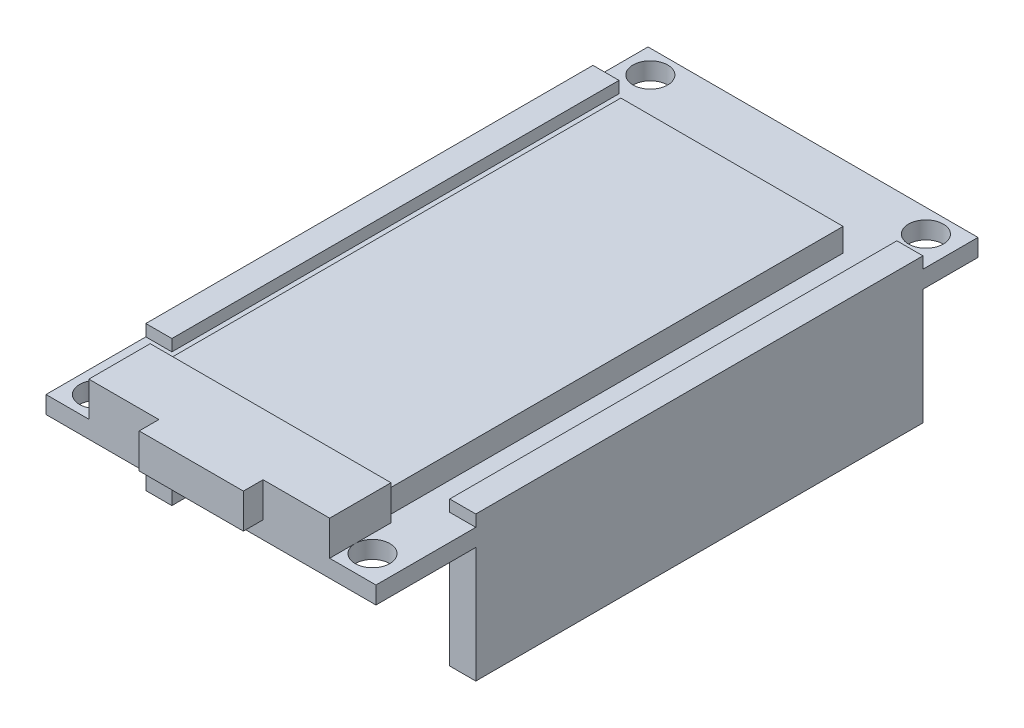
SolidWorks part; units mm, degrees
other "Исправление1"
sketch "Эскиз7"
ref_plane "Спереди" through (0, 0, 0) normal (0, 0, 1) x (1, 0, 0)
ref_plane "Сверху" through (0, 0, 0) normal (0, 1, 0) x (1, 0, 0)
ref_plane "Справа" through (0, 0, 0) normal (1, 0, 0) x (0, 0, -1)
other "Configuration Table"
sketch "Эскиз2" plane through (0, 0, 0) normal (0, 1, 0) x (1, 0, 0)
  line L0 (0.2951, -47.7) -> (-4.7049, -47.7) construction
  line L1 (0, 0) -> (28.5, 0)
  line L2 (0, 0) -> (0, -52)
  line L3 (0, -52) -> (28.5, -52)
  line L4 (28.5, 0) -> (28.5, -52)
  line L5 (29.7573, -47.7) -> (24.7573, -47.7) construction
  line L6 (28.9793, -47.7) -> (23.9793, -47.7) construction
  circle A1 centre (2.2, -2) radius 1.5
  circle A2 centre (26, -2) radius 1.5
  circle A4 centre (2.2, -49.8) radius 1.5
  circle A5 centre (26, -49.8) radius 1.5
  point P4 (2.2, -49.8)
  point P10 (0, 0)
  point P13 (0, 0)
  point P16 (0, 0)
  point P17 (2.2, -49.8)
  dimension "D3" = 2
  dimension "D4" = 2.2
  dimension "D5" = 2.5
  dimension "D6" = 2
  dimension "D7" = 3
  dimension "D8" = 3
  dimension "D9" = 3
  dimension "D10" = 2.2
  dimension "D11" = 2.5
  dimension "D12" = 3
  dimension "D1" = 28.5
  dimension "D2" = 52
extrude "Бобышка-Вытянуть1" add sketch "Эскиз2" along normal blind 1.5
sketch3d "Трехмерный эскиз1"
  line L0 (0, 1.5, 0) -> (0, 1.5, 52) construction
  line L2 (9.75, 1.5, 46.7) -> (9.75, 1.5, 53.7)
  line L3 (9.75, 1.5, 46.7) -> (18.75, 1.5, 46.7)
  line L4 (18.75, 1.5, 46.7) -> (18.75, 1.5, 53.7)
  line L5 (9.75, 1.5, 53.7) -> (18.75, 1.5, 53.7)
  line L6 (0, 1.5, 52) -> (28.5, 1.5, 52) construction
  dimension "D1" = 9
  dimension "D2" = 1.7
  dimension "D3" = 9.75
  dimension "D4" = 7
extrude "Бобышка-Вытянуть2" add sketch "Трехмерный эскиз1" along direction (0, -1, 0) on the side against the normal blind 3
sketch "Эскиз3" plane through (0, 1.5, 0) normal (0, 1, 0) x (1, 0, 0)
  line L0 (0, -52) -> (9.75, -52) construction
  line L5 (4.4, -46.7) -> (7.4, -46.7)
  line L6 (4.4, -46.7) -> (4.4, -51)
  line L7 (4.4, -51) -> (7.4, -51)
  line L8 (7.4, -46.7) -> (7.4, -51)
  line L9 (14.25, 0) -> (14.25, -58.4604) construction
  line L10 (28.5, 0) -> (0, 0) construction
  line L11 (24.1, -51) -> (21.1, -51)
  line L12 (21.1, -46.7) -> (21.1, -51)
  line L13 (24.1, -46.7) -> (21.1, -46.7)
  line L14 (24.1, -46.7) -> (24.1, -51)
  line L15 (18.75, -46.7) -> (18.75, -52)
  line L16 (18.75, -52) -> (24.5, -52)
  line L17 (18.75, -52) -> (28.5, -52) construction
  line L18 (24.5, -52) -> (24.5, -46.7)
  line L19 (24.5, -46.7) -> (18.75, -46.7)
  line L20 (9.75, -46.7) -> (3.7, -46.7)
  line L21 (3.7, -46.7) -> (3.7, -52)
  line L22 (3.7, -52) -> (9.75, -52)
  line L23 (9.75, -52) -> (9.75, -46.7)
  circle A0 centre (2.2, -49.8) radius 1.5 construction
  circle A1 centre (26, -49.8) radius 1.5 construction
  dimension "D4" = 2.2
  dimension "D1" = 3
  dimension "D2" = 1
  dimension "D3" = 4.3
extrude "Бобышка-Вытянуть5" add sketch "Эскиз3" along normal blind 3 contours L19 L15 L16 L18 | L23 L20 L21 L22
sketch "Эскиз5" plane through (0, 1.5, 0) normal (0, 1, 0) x (1, 0, 0)
  line L0 (0, 0) -> (0, -52) construction
  line L1 (5.5, -26.5) -> (23, -26.5)
  line L2 (5.5, -26.5) -> (5.5, -7)
  line L3 (5.5, -7) -> (23, -7)
  line L4 (23, -26.5) -> (23, -7)
  line L5 (28.5, -52) -> (28.5, 0) construction
  line L6 (28.5, 0) -> (0, 0) construction
  line L7 (4.65, -46.7) -> (4.65, -7)
  line L8 (4.65, -7) -> (23.85, -7)
  line L9 (23.85, -7) -> (23.85, -46.7)
  line L10 (23.85, -46.7) -> (4.65, -46.7)
  line L11 (3.7, -52) -> (9.75, -52) construction
  dimension "D1" = 5.5
  dimension "D2" = 5.5
  dimension "D3" = 7
  dimension "D4" = 19.5
  dimension "D5" = 4.65
  dimension "D6" = 4.65
  dimension "D7" = 5.3
extrude "Бобышка-Вытянуть6" add sketch "Эскиз5" along normal blind 2 contours L10 L7 L8 L9
sketch "Эскиз6" plane through (0, 1.5, 0) normal (0, 1, 0) x (1, 0, 0)
  line L0 (0, -4.7572) -> (2.25, -4.7572)
  line L1 (0, 0) -> (0, -52) construction
  line L2 (2.25, -4.7572) -> (2.25, -43.3778)
  line L3 (2.25, -43.3778) -> (0, -43.3778)
  line L4 (0, -43.3778) -> (0, -4.7572)
  line L5 (14.25, 0) -> (14.25, -55.5138) construction
  line L6 (28.5, 0) -> (0, 0) construction
  line L7 (26.25, -43.3778) -> (28.5, -43.3778)
  line L8 (26.25, -4.7572) -> (26.25, -43.3778)
  line L9 (28.5, -4.7572) -> (26.25, -4.7572)
  line L10 (28.5, -43.3778) -> (28.5, -4.7572)
  point P14 (0, 0)
  point P15 (0, 0)
  point P16 (0, 0)
  line M15 (28.5, -52) -> (28.5, 0)
  dimension "D1" = 2.25
  dimension "D2" = 38.6206
  dimension "D3" = 4.7572
extrude "Бобышка-Вытянуть7" add sketch "Эскиз6" along normal blind 1 contours L9 L8 L7 M15 | L4 L0 L2 L3 region at (27.375, 1.5, 24.0675)
extrude "Бобышка-Вытянуть8" add sketch "Эскиз6<3>" against normal blind 11.5
sketch "Эскиз6<3>" plane through (0, 1.5, 0) normal (0, 1, 0) x (1, 0, 0) same geometry as "Эскиз6"
